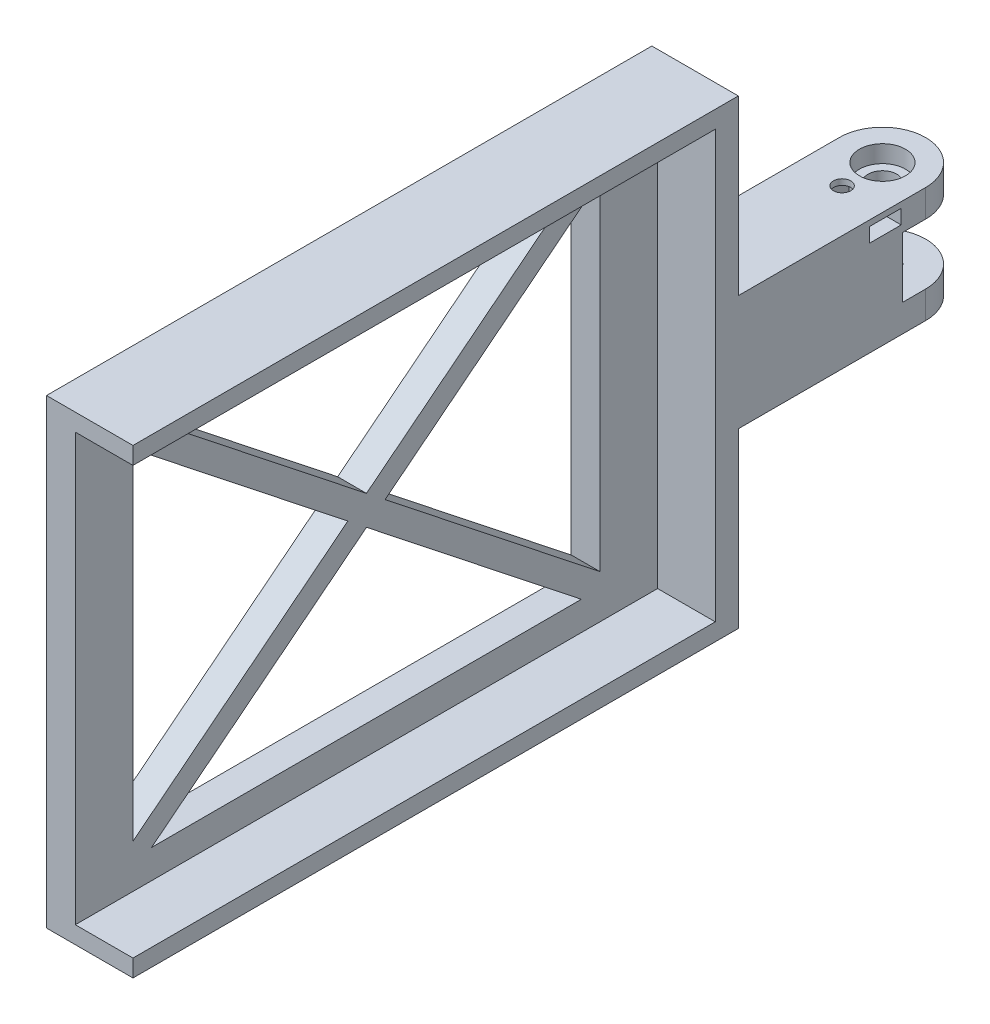
SolidWorks part; units mm, degrees
ref_plane "Front Plane" through (0, 0, 0) normal (0, 0, 1) x (1, 0, 0)
ref_plane "Top Plane" through (0, 0, 0) normal (0, 1, 0) x (1, 0, 0)
ref_plane "Right Plane" through (0, 0, 0) normal (1, 0, 0) x (0, 0, -1)
sketch "Sketch1" plane through (0, 0, 0) normal (0, 0, 1) x (1, 0, 0)
  line L1 (7.5, -10) -> (-7.5, -10)
  line L2 (7.5, -10) -> (7.5, 10)
  line L3 (7.5, 10) -> (-7.5, 10)
  line L4 (-7.5, -10) -> (-7.5, 10)
  line L5 (7.5, -10) -> (-7.5, 10) construction
  line L6 (7.5, 10) -> (-7.5, -10) construction
  point P0 (0, 0)
  dimension "D1" = 15
  dimension "D2" = 20
extrude "Boss-Extrude1" add sketch "Sketch1" along normal mid plane 40
sketch "Sketch2" plane through (0, -10, 0) normal (0, -1, 0) x (1, 0, 0)
  line L0 (-7.5, 20) -> (7.5, 20) construction
  point P4 (0, 20)
fillet "Fillet1" radius 7.5 2 edges at (-7.5, 0, -20) (7.5, 0, -20)
sketch "Sketch3" plane through (0, 10, 0) normal (0, 1, 0) x (1, 0, 0)
  circle A0 centre (0, 12.5) radius 8.5
  arc A1 (7.5, 12.5) -> (0, 20) centre (0, 12.5) ccw construction
  dimension "D1" = 1
extrude "Cut-Extrude1" cut sketch "Sketch3" against normal blind 10.5 from offset 4.75 offset against normal yes
sketch "Sketch4" plane through (0, 10, 0) normal (0, 1, 0) x (1, 0, 0)
  circle A0 centre (0, 12.5) radius 2.5
  dimension "D1" = 5
extrude "Cut-Extrude2" cut sketch "Sketch4" against normal through all
sketch "Sketch5" plane through (0, -10, 0) normal (0, -1, 0) x (-1, 0, 0)
  line L1 (-2.0207, 16) -> (-4.0415, 12.5)
  line L2 (-4.0415, 12.5) -> (-2.0207, 9)
  line L3 (-2.0207, 9) -> (2.0207, 9)
  line L4 (2.0207, 9) -> (4.0415, 12.5)
  line L5 (4.0415, 12.5) -> (2.0207, 16)
  line L6 (2.0207, 16) -> (-2.0207, 16)
  circle A0 centre (0, 12.5) radius 3.5 construction
  dimension "D1" = 7
extrude "Cut-Extrude3" cut sketch "Sketch5" against normal blind 3
sketch "Sketch6" plane through (0, 10, 0) normal (0, 1, 0) x (1, 0, 0)
  circle A0 centre (0, 12.5) radius 4
  dimension "D1" = 8
extrude "Cut-Extrude4" cut sketch "Sketch6" against normal blind 3
sketch "Sketch7" plane through (-7.5, 0, 0) normal (-1, 0, 0) x (0, 0, 1)
  line L0 (20, 10) -> (20, -10) construction
  line L1 (125, 40) -> (20, 40)
  line L2 (125, 40) -> (125, -40)
  line L3 (125, -40) -> (20, -40)
  line L4 (20, 40) -> (20, -40)
  line L5 (125, 40) -> (20, -40) construction
  line L6 (125, -40) -> (20, 40) construction
  point P0 (72.5, 0)
  point P5 (0, 0)
  dimension "D1" = 105
  dimension "D2" = 80
extrude "Boss-Extrude2" add sketch "Sketch7" against normal blind 15
sketch "Sketch9" plane through (7.5, 0, 0) normal (1, 0, 0) x (0, 0, -1)
  line L0 (-125, -40) -> (-125, 40) construction
  line L1 (-24, 37) -> (-125, 37)
  line L2 (-24, 37) -> (-24, -37)
  line L3 (-24, -37) -> (-125, -37)
  line L4 (-125, 37) -> (-125, -37)
  line L5 (-24, 37) -> (-125, -37) construction
  line L6 (-24, -37) -> (-125, 37) construction
  line L7 (-20, -40) -> (-125, -40) construction
  line L8 (-20, -10) -> (-20, -40) construction
  point P0 (-74.5, 0)
  point P7 (0, 0)
  dimension "D1" = 3
  dimension "D2" = 4
extrude "Cut-Extrude5" cut sketch "Sketch9" against normal blind 10
sketch "Sketch10" plane through (-2.5, 0, 0) normal (1, 0, 0) x (0, 0, -1)
  line L0 (-125, 37) -> (-125, -37) construction
  line L1 (-34, 32) -> (-115, 32) construction
  line L2 (-34, 32) -> (-34, -32) construction
  line L3 (-34, -32) -> (-115, -32) construction
  line L4 (-115, 32) -> (-115, -32) construction
  line L5 (-34, 32) -> (-115, -32) construction
  line L6 (-34, -32) -> (-115, 32) construction
  line L7 (-24, -37) -> (-24, 37) construction
  line L8 (-111.774, -32) -> (-74.5, -2.549)
  line L9 (-74.5, -2.549) -> (-37.226, -32)
  line L10 (-37.226, -32) -> (-111.774, -32)
  line L11 (-125, -37) -> (-24, -37) construction
  line L12 (-115, -29.451) -> (-77.726, 0)
  line L13 (-77.726, 0) -> (-115, 29.451)
  line L14 (-115, 29.451) -> (-115, -29.451)
  line L15 (-74.5, 0) -> (-74.5, 32) construction
  line L16 (-74.5, 0) -> (-34, 0) construction
  line L17 (-37.226, 32) -> (-111.774, 32)
  line L18 (-74.5, 2.549) -> (-37.226, 32)
  line L19 (-111.774, 32) -> (-74.5, 2.549)
  line L20 (-71.274, 0) -> (-34, 29.451)
  line L21 (-34, -29.451) -> (-71.274, 0)
  line L22 (-34, 29.451) -> (-34, -29.451)
  point P0 (-74.5, 0)
  point P15 (0, 0)
  dimension "D1" = 10
  dimension "D2" = 10
  dimension "D3" = 2
  dimension "D4" = 5
  dimension "D5" = 4
  dimension "D6" = 2
extrude "Cut-Extrude6" cut sketch "Sketch10" against normal through all
sketch "Sketch12" plane through (0, 10, 0) normal (0, 1, 0) x (1, 0, 0)
  line L0 (7.5, -20) -> (7.5, 12.5) construction
  line L1 (-1.5877, 8.25) -> (-3.1754, 5.5)
  line L2 (-3.1754, 5.5) -> (-1.5877, 2.75)
  line L3 (-1.5877, 2.75) -> (1.5877, 2.75)
  line L4 (1.5877, 2.75) -> (3.1754, 5.5) construction
  line L5 (3.1754, 5.5) -> (1.5877, 8.25) construction
  line L6 (1.5877, 8.25) -> (-1.5877, 8.25)
  line L7 (1.5877, 8.25) -> (7.5, 8.25)
  line L9 (1.5877, 2.75) -> (7.5, 2.75)
  line L10 (7.5, 8.25) -> (7.5, 2.75)
  line L11 (1.5877, 8.25) -> (7.5, 2.75) construction
  line L12 (1.5877, 2.75) -> (7.5, 8.25) construction
  circle A0 centre (0, 5.5) radius 2.75 construction
  point P1 (0, 12.5)
  point P11 (4.5439, 5.5)
  dimension "D1" = 7
  dimension "D2" = 5.5
extrude "Cut-Extrude7" cut sketch "Sketch12" against normal blind 2.5 from offset 1 offset against normal yes
sketch "Sketch13" plane through (0, 10, 0) normal (0, 1, 0) x (1, 0, 0)
  circle A0 centre (0, 5.5) radius 1.5
  point P2 (0, 0)
  point P5 (0, 12.5)
  dimension "D2" = 3
  dimension "D1" = 7
extrude "Cut-Extrude8" cut sketch "Sketch13" against normal blind 7
